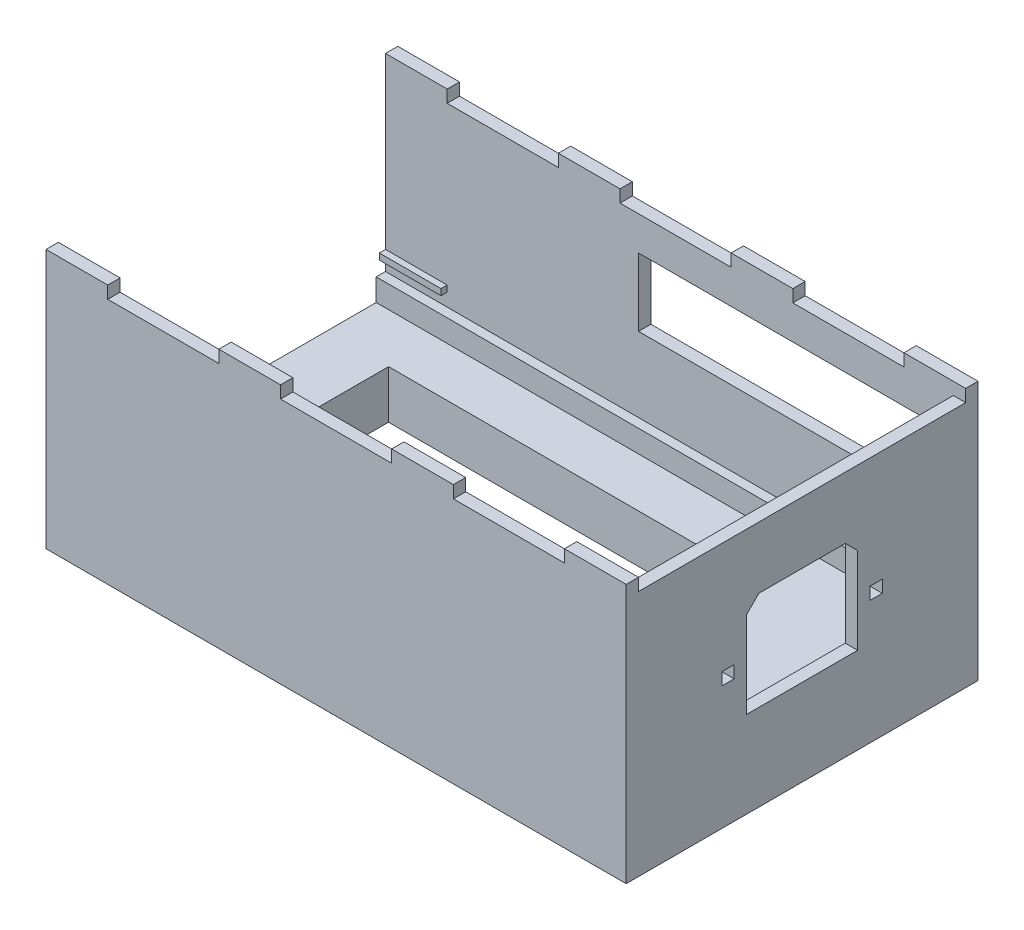
SolidWorks part; units mm, degrees
ref_plane "Front Plane" through (0, 0, 0) normal (0, 0, 1) x (1, 0, 0)
ref_plane "Top Plane" through (0, 0, 0) normal (0, 1, 0) x (1, 0, 0)
ref_plane "Right Plane" through (0, 0, 0) normal (1, 0, 0) x (0, 0, -1)
sketch "Sketch1" plane through (0, 0, 0) normal (0, 1, 0) x (1, 0, 0)
  line L1 (-30.298, 32.6459) -> (63.702, 32.6459)
  line L2 (-30.298, 32.6459) -> (-30.298, -24.3541)
  line L3 (-30.298, -24.3541) -> (63.702, -24.3541)
  line L4 (63.702, 32.6459) -> (63.702, -24.3541)
  dimension "D1" = 94
  dimension "D2" = 57
extrude "Boss-Extrude1" add sketch "Sketch1" along normal blind 10
sketch "Sketch2" plane through (0, 10, 0) normal (0, 1, 0) x (1, 0, 0)
  line L0 (-30.298, 32.6459) -> (63.702, 32.6459)
  line L1 (63.702, 32.6459) -> (63.702, -24.3541)
  line L2 (63.702, -24.3541) -> (-30.298, -24.3541)
  line L3 (-30.298, -24.3541) -> (-30.298, -22.3541)
  line L4 (-30.298, 32.6459) -> (-30.298, -24.3541) construction
  line L5 (-30.298, -22.3541) -> (61.702, -22.3541)
  line L6 (61.702, -22.3541) -> (61.702, 30.6459)
  line L7 (61.702, 30.6459) -> (-30.298, 30.6459)
  line L8 (-30.298, 30.6459) -> (-30.298, 32.6459)
  dimension "D1" = 2
  dimension "D2" = 2
  dimension "D3" = 2
extrude "Boss-Extrude2" add sketch "Sketch2" along normal blind 30
sketch "Sketch3" plane through (-30.298, 0, 0) normal (-1, 0, 0) x (0, 0, 1)
  line L0 (-30.6459, 40) -> (-30.6459, 10) construction
  line L1 (-30.6459, 10) -> (-29.1459, 10)
  line L2 (-30.6459, 10) -> (-30.6459, 11.4)
  line L3 (-30.6459, 11.4) -> (-29.1459, 11.4)
  line L4 (-29.1459, 10) -> (-29.1459, 11.4)
  line L5 (22.3541, 10) -> (20.8541, 10)
  line L6 (22.3541, 10) -> (22.3541, 11.4)
  line L7 (22.3541, 11.4) -> (20.8541, 11.4)
  line L8 (20.8541, 10) -> (20.8541, 11.4)
  line L9 (-30.6459, 14.5) -> (-29.6459, 14.5)
  line L10 (-30.6459, 14.5) -> (-30.6459, 13.5)
  line L11 (-30.6459, 13.5) -> (-29.6459, 13.5)
  line L12 (-29.6459, 14.5) -> (-29.6459, 13.5)
  line L13 (22.3541, 40) -> (22.3541, 10) construction
  line L14 (22.3541, 13.5) -> (21.3541, 13.5)
  line L15 (22.3541, 13.5) -> (22.3541, 14.5)
  line L16 (22.3541, 14.5) -> (21.3541, 14.5)
  line L17 (21.3541, 13.5) -> (21.3541, 14.5)
  dimension "D1" = 1.5
  dimension "D2" = 1.4
  dimension "D3" = 1.5
  dimension "D4" = 1.4
  dimension "D5" = 2.1
  dimension "D6" = 2.1
  dimension "D8" = 1
  dimension "D9" = 1
  dimension "D10" = 1
  dimension "D11" = 1
extrude "Boss-Extrude3" add sketch "Sketch3" against normal up to surface (92 mm away) contours L1 L4 L3 L2 | L5 L8 L7 L6 | L17 L16 L15 L14 up to face at (61.702, 25, -4.1459)
extrude "Boss-Extrude4" add sketch "Sketch3<3>" against normal blind 10 contours L12 L11 L10 L9
sketch "Sketch3<3>" plane through (-30.298, 0, 0) normal (-1, 0, 0) x (0, 0, 1) same geometry as "Sketch3"
sketch "Sketch4" plane through (0, 0, -32.6459) normal (0, 0, -1) x (-1, 0, 0)
  line L0 (-63.702, 40) -> (-63.702, 0) construction
  line L1 (-56.702, 34.5) -> (-10.702, 34.5)
  line L2 (-56.702, 34.5) -> (-56.702, 23.5)
  line L3 (-56.702, 23.5) -> (-10.702, 23.5)
  line L4 (-10.702, 34.5) -> (-10.702, 23.5)
  point P4 (-56.702, 29)
  dimension "D1" = 7
  dimension "D2" = 46
  dimension "D3" = 11
  dimension "D4" = 9
extrude "Cut-Extrude1" cut sketch "Sketch4" against normal blind 10
sketch "Sketch5" plane through (63.702, 0, 0) normal (1, 0, 0) x (0, 0, -1)
  line L0 (-4.8541, 21) -> (13.1459, 21) construction
  line L1 (-2.8541, 30) -> (11.1459, 30)
  line L2 (-4.8541, 28) -> (-4.8541, 14)
  line L3 (-4.8541, 14) -> (13.1459, 14)
  line L4 (13.1459, 28) -> (13.1459, 14)
  line L5 (-24.3541, 40) -> (32.6459, 40) construction
  line L6 (4.1459, 40) -> (4.1459, 0) construction
  line L7 (-4.8541, 21) -> (-24.3541, 21) construction
  line L8 (-24.3541, 0) -> (32.6459, 0) construction
  line L9 (-24.3541, 40) -> (-24.3541, 0) construction
  line L10 (13.1459, 21) -> (32.6459, 21) construction
  line L11 (32.6459, 40) -> (32.6459, 0) construction
  line L12 (11.1459, 30) -> (13.1459, 28)
  line L13 (-8.8541, 22) -> (-6.8541, 22)
  line L14 (-8.8541, 22) -> (-8.8541, 20)
  line L15 (-8.8541, 20) -> (-6.8541, 20)
  line L16 (-6.8541, 22) -> (-6.8541, 20)
  line L17 (15.1459, 22) -> (17.1459, 22)
  line L18 (15.1459, 22) -> (15.1459, 20)
  line L19 (15.1459, 20) -> (17.1459, 20)
  line L20 (17.1459, 22) -> (17.1459, 20)
  line L21 (-4.8541, 28) -> (-2.8541, 30)
  point P10 (4.1459, 30)
  point P27 (-6.8541, 21)
  point P28 (17.1459, 21)
  dimension "D1" = 0
  dimension "D3" = 10
  dimension "D5" = 2
  dimension "D6" = 0
  dimension "D7" = 2
  dimension "D8" = 2
  dimension "D9" = 2
  dimension "D10" = 2
  dimension "D11" = 0
  dimension "D12" = 2
  dimension "D13" = 45
  dimension "D15" = 45
extrude "Cut-Extrude2" cut sketch "Sketch5" against normal up to surface (2 mm away) up to face at (61.702, 16.8, 4.5207)
ref_plane "Plane5" through (0, 33, 0) normal (0, 1, 0) x (1, 0, 0)
sketch "Sketch7" plane through (0, 33, 0) normal (0, 1, 0) x (1, 0, 0)
  line L0 (61.702, -22.3541) -> (-30.298, -22.3541) construction
  line L1 (10.702, -22.3541) -> (61.702, -22.3541)
  line L2 (10.702, -22.3541) -> (10.702, -20.3541)
  line L3 (10.702, -20.3541) -> (59.702, -20.3541)
  line L4 (61.702, -22.3541) -> (61.702, -20.3541)
  line L5 (61.702, 29.1459) -> (61.702, -20.8541) construction
  line L6 (61.702, 30.6459) -> (61.702, -22.3541) construction
  line L8 (59.702, -20.3541) -> (59.702, 15.6459)
  line L9 (59.702, 15.6459) -> (61.702, 15.6459)
  line L10 (61.702, -20.3541) -> (61.702, 15.6459)
  dimension "D1" = 51
  dimension "D2" = 2
  dimension "D3" = 38
  dimension "D4" = 2
extrude "Boss-Extrude5" add sketch "Sketch7" against normal blind 2 contours L3 L8 L9 L10 L4 L1 L2
fillet "Fillet1" radius 1.5 2 edges at (59.702, 31, 2.3541) (35.202, 31, 20.3541) conic radius 3
ref_plane "Plane6" through (0, 34.8, 0) normal (0, 1, 0) x (1, 0, 0)
sketch "Sketch8" plane through (0, 34.8, 0) normal (0, 1, 0) x (1, 0, 0)
  line L1 (10.702, -20.3541) -> (59.702, -20.3541)
  line L2 (10.702, -20.3541) -> (10.702, -22.3541)
  line L3 (10.702, -22.3541) -> (61.702, -22.3541)
  line L4 (61.702, -20.3541) -> (61.702, -22.3541)
  line L5 (61.702, -22.3541) -> (59.702, -22.3541)
  line L6 (61.702, -22.3541) -> (61.702, 15.6459)
  line L7 (61.702, 15.6459) -> (59.702, 15.6459)
  line L8 (59.702, -20.3541) -> (59.702, 15.6459)
extrude "Boss-Extrude6" add sketch "Sketch8" along normal blind 1 contours L6 L7 L8 L1 L2 L3
sketch "Sketch9" plane through (0, 40, 0) normal (0, 1, 0) x (1, 0, 0)
  line L0 (-30.298, 30.6459) -> (61.702, 30.6459) construction
  line L1 (-30.298, 32.6459) -> (-20.298, 32.6459)
  line L2 (-30.298, 32.6459) -> (-30.298, 30.6459)
  line L3 (-30.298, 30.6459) -> (-20.298, 30.6459)
  line L4 (-20.298, 32.6459) -> (-20.298, 30.6459)
  line L5 (61.702, 30.6459) -> (-30.298, 30.6459) construction
  line L6 (-2.298, 30.6459) -> (7.702, 30.6459)
  line L7 (-2.298, 30.6459) -> (-2.298, 32.6459)
  line L8 (-2.298, 32.6459) -> (7.702, 32.6459)
  line L9 (7.702, 30.6459) -> (7.702, 32.6459)
  line L10 (63.702, 32.6459) -> (-30.298, 32.6459) construction
  line L11 (61.702, -22.3541) -> (-30.298, -22.3541) construction
  line L12 (25.702, 30.6459) -> (35.702, 30.6459)
  line L13 (25.702, 30.6459) -> (25.702, 32.6459)
  line L14 (25.702, 32.6459) -> (35.702, 32.6459)
  line L15 (35.702, 30.6459) -> (35.702, 32.6459)
  line L16 (53.702, 30.6459) -> (63.702, 30.6459)
  line L17 (53.702, 30.6459) -> (53.702, 32.6459)
  line L18 (53.702, 32.6459) -> (63.702, 32.6459)
  line L19 (63.702, 30.6459) -> (63.702, 32.6459)
  line L20 (-30.298, -24.3541) -> (-20.298, -24.3541)
  line L21 (-30.298, -24.3541) -> (-30.298, -22.3541)
  line L22 (-30.298, -22.3541) -> (-20.298, -22.3541)
  line L23 (-20.298, -24.3541) -> (-20.298, -22.3541)
  line L24 (-30.298, -24.3541) -> (63.702, -24.3541) construction
  line L25 (-2.298, -24.3541) -> (7.702, -24.3541)
  line L26 (-2.298, -24.3541) -> (-2.298, -22.3541)
  line L27 (-2.298, -22.3541) -> (7.702, -22.3541)
  line L28 (7.702, -24.3541) -> (7.702, -22.3541)
  line L29 (10.702, -22.3541) -> (61.702, -22.3541) construction
  line L30 (25.702, -24.3541) -> (35.702, -24.3541)
  line L31 (25.702, -24.3541) -> (25.702, -22.3541)
  line L32 (25.702, -22.3541) -> (35.702, -22.3541)
  line L33 (35.702, -24.3541) -> (35.702, -22.3541)
  line L35 (63.702, -24.3541) -> (53.702, -24.3541)
  line L36 (63.702, -24.3541) -> (63.702, -22.3541)
  line L37 (63.702, -22.3541) -> (53.702, -22.3541)
  line L38 (53.702, -24.3541) -> (53.702, -22.3541)
  dimension "D1" = 10
  dimension "D2" = 10
  dimension "D3" = 18
  dimension "D4" = 18
  dimension "D5" = 10
  dimension "D6" = 18
  dimension "D7" = 18
  dimension "D8" = 18
  dimension "D9" = 18
  dimension "D10" = 10
  dimension "D11" = 10
  dimension "D12" = 10
extrude "Boss-Extrude7" add sketch "Sketch9" along normal blind 2
sketch "Sketch10" plane through (0, 10, 0) normal (0, 1, 0) x (1, 0, 0)
  line L0 (-30.298, 4.1459) -> (61.702, 4.1459) construction
  line L1 (-20.298, 21.1459) -> (31.702, 21.1459)
  line L2 (-20.298, 21.1459) -> (-20.298, -12.8541)
  line L3 (-20.298, -12.8541) -> (31.702, -12.8541)
  line L4 (31.702, 21.1459) -> (31.702, -12.8541)
  line L5 (-30.298, 29.1459) -> (-30.298, -20.8541) construction
  line L6 (61.702, 30.6459) -> (61.702, -22.3541) construction
  point P10 (31.702, 4.1459)
  dimension "D1" = 34
  dimension "D2" = 0
  dimension "D3" = 52
  dimension "D4" = 10
extrude "Cut-Extrude3" cut sketch "Sketch10" against normal through all and the other way through all
sketch "Sketch11" plane through (0, 10, 0) normal (0, 1, 0) x (1, 0, 0)
  line L1 (61.702, 29.1459) -> (-30.298, 29.1459)
  line L2 (61.702, 29.1459) -> (61.702, -20.8541)
  line L3 (61.702, -20.8541) -> (-30.298, -20.8541)
  line L4 (-30.298, 29.1459) -> (-30.298, -20.8541)
extrude "Cut-Extrude4" cut sketch "Sketch11" against normal blind 2.2
sketch "Sketch12" plane through (63.702, 0, 0) normal (1, 0, 0) x (0, 0, -1)
  line L0 (17.1459, 20) -> (17.1459, 22) construction
  line L1 (-8.8541, 30) -> (17.1459, 30)
  line L2 (-8.8541, 30) -> (-8.8541, 14)
  line L3 (-8.8541, 14) -> (17.1459, 14)
  line L4 (17.1459, 30) -> (17.1459, 14)
  line L5 (-8.8541, 22) -> (-8.8541, 20) construction
  line L6 (-4.8541, 14) -> (13.1459, 14) construction
  line L7 (11.1459, 30) -> (-2.8541, 30) construction
  line L9 (-4.8541, 14) -> (-4.8541, 30) construction
  line L10 (13.1459, 14) -> (13.1459, 30) construction
  line L11 (-6.8541, 20) -> (-6.8541, 22) construction
  dimension "D1" = 0
  dimension "D2" = 0
  dimension "D3" = 0
  dimension "D4" = 0
  dimension "D5" = 2
  dimension "D6" = 16
  dimension "D7" = 16
  dimension "D8" = 26
  dimension "D9" = 18
  dimension "D10" = 16
ref_plane "Plane9" through (63.702, 28, 4.8541) normal (0, -1, 0) x (-1, 0, 0)
